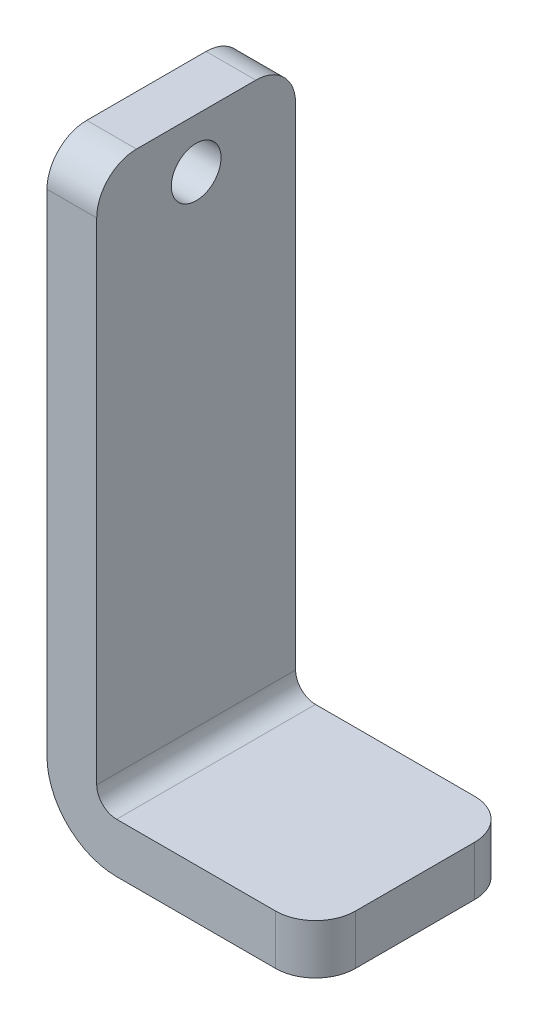
SolidWorks part; units mm, degrees
material "6061 Alloy"
ref_plane "Front Plane" through (0, 0, 0) normal (0, 0, 1) x (1, 0, 0)
ref_plane "Top Plane" through (0, 0, 0) normal (0, 1, 0) x (1, 0, 0)
ref_plane "Right Plane" through (0, 0, 0) normal (1, 0, 0) x (0, 0, -1)
sketch "Sketch1" plane through (0, 0, 0) normal (0, 0, 1) x (1, 0, 0)
  line L0 (0, 22.4958) -> (0, -11.3863)
  line L1 (1.27, -12.6563) -> (13.97, -12.6563)
  line L2 (-3.175, 22.4958) -> (-3.175, -11.3863)
  line L3 (1.27, -15.8313) -> (13.97, -15.8313)
  line L4 (0, 22.4958) -> (-3.175, 22.4958)
  line L5 (13.97, -12.6563) -> (13.97, -15.8313)
  arc A0 (1.27, -12.6563) -> (0, -11.3863) centre (1.27, -11.3863) cw
  arc A1 (1.27, -15.8313) -> (-3.175, -11.3863) centre (1.27, -11.3863) cw
  dimension "D1" = 1.27
  dimension "D3" = 12.7
  dimension "D4" = 38.3271
  dimension "D2" = 3.175
extrude "Boss-Extrude1" add sketch "Sketch1" along normal blind 12.7
fillet "Fillet1" radius 2.54 4 edges at (13.97, -14.2438, 0) (13.97, -14.2438, 12.7) (-1.5875, 22.4958, 0) (-1.5875, 22.4958, 12.7)
sketch "Sketch2" plane through (-3.175, 0, 0) normal (-1, 0, 0) x (0, 0, 1)
  line L0 (10.16, 22.4958) -> (2.54, 22.4958) construction
  line L1 (10.16, 22.4958) -> (2.54, 22.4958) construction
  line L6 (3.7, 16.4767) -> (4.353, 4.5267)
  line L7 (9, 16.4767) -> (8.347, 4.5267)
  circle A0 centre (6.35, 18.6858) radius 1.143
  arc A6 (9, 16.4767) -> (3.7, 16.4767) centre (6.35, 18.6858) ccw
  arc A7 (4.353, 4.5267) -> (8.347, 4.5267) centre (6.35, 4.6358) ccw
  circle A11 centre (6.35, 4.2358) radius 0.6
  circle A15 centre (6.35, 8.2358) radius 0.6
  circle A17 centre (6.35, 12.2358) radius 0.6
  point P13 (6.35, 22.4958)
  dimension "D1" = 6.9
  dimension "D2" = 4
  dimension "D7" = 1.2
  dimension "D8" = 6.45
  dimension "D10" = 2.286
  dimension "D3" = 11.95
  dimension "D4" = 0.653
  dimension "D5" = 5.3
  dimension "D6" = 3.994
  dimension "D9" = 4
  dimension "D11" = 4
  dimension "D12" = 3.81
sketch "Sketch3" plane through (-3.175, 0, 0) normal (-1, 0, 0) x (0, 0, 1)
  line L0 (6.35, 22.4958) -> (6.35, -11.3863)
  line L1 (10.16, 22.4958) -> (2.54, 22.4958) construction
  line L2 (12.7, -11.3863) -> (0, -11.3863) construction
sketch "Sketch5" plane through (-3.175, 0, 0) normal (-1, 0, 0) x (0, 0, 1)
  line L0 (6.35, 22.4958) -> (6.35, 19.3208)
  line L4 (10.16, 22.4958) -> (2.54, 22.4958)
  line L5 (0, 19.9558) -> (0, -11.3863)
  line L6 (0, -11.3863) -> (12.7, -11.3863)
  line L7 (12.7, -11.3863) -> (12.7, 19.9558)
  line L8 (10.16, 22.4958) -> (2.54, 22.4958)
  line L9 (0, 19.9558) -> (0, -11.3863)
  line L10 (0, -11.3863) -> (12.7, -11.3863)
  line L11 (12.7, -11.3863) -> (12.7, 19.9558)
  arc A2 (2.54, 22.4958) -> (0, 19.9558) centre (2.54, 19.9558) ccw
  arc A3 (12.7, 19.9558) -> (10.16, 22.4958) centre (10.16, 19.9558) ccw
  arc A4 (2.54, 22.4958) -> (0, 19.9558) centre (2.54, 19.9558) ccw
  arc A5 (12.7, 19.9558) -> (10.16, 22.4958) centre (10.16, 19.9558) ccw
  circle A6 centre (6.35, 19.3208) radius 1.5875
  dimension "D2" = 3.175
  dimension "D3" = 3.175
  dimension "D1" = 0
extrude "Cut-Extrude2" cut sketch "Sketch5" against normal up to next from surface contours A6 region at (-3.175, 20.4116, 7.4408) starting at face at (-3.175, 10.5305, 6.35)
